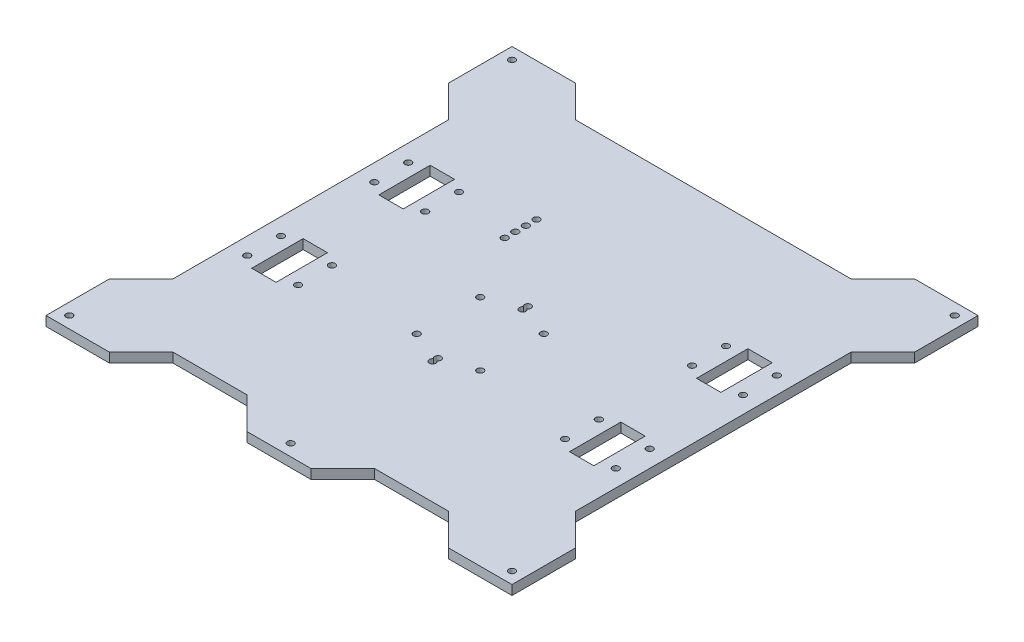
SolidWorks part; units mm, degrees
ref_plane "Front Plane" through (0, 0, 0) normal (0, 0, 1) x (1, 0, 0)
ref_plane "Top Plane" through (0, 0, 0) normal (0, 1, 0) x (1, 0, 0)
ref_plane "Right Plane" through (0, 0, 0) normal (1, 0, 0) x (0, 0, -1)
sketch "Sketch1" plane through (0, 0, 0) normal (0, 1, 0) x (1, 0, 0)
  line L1 (-110, 110) -> (110, 110)
  line L2 (-110, 110) -> (-110, -110)
  line L3 (-110, -110) -> (110, -110)
  line L4 (110, 110) -> (110, -110)
  line L5 (-110, 110) -> (110, -110) construction
  line L6 (-110, -110) -> (110, 110) construction
  point P0 (0, 0)
  dimension "D1" = 220
  dimension "D2" = 220
extrude "Square" add sketch "Sketch1" along normal blind 4.5
sketch "Sketch2" plane through (0, 4.5, 0) normal (0, 1, 0) x (1, 0, 0)
  line L0 (0, 110) -> (0, -110) construction
  line L1 (110, 110) -> (-110, 110) construction
  line L2 (-110, -110) -> (110, -110) construction
  line L3 (-110, 0) -> (110, 0) construction
  line L4 (-110, 110) -> (-110, -110) construction
  line L5 (110, -110) -> (110, 110) construction
  line L6 (75, 110) -> (75, -110) construction
  line L7 (75, 30) -> (0, 30) construction
  line L8 (75, -30) -> (0, -30) construction
  circle A0 centre (87, 38) radius 1.55
  circle A1 centre (87, 22) radius 1.55
  circle A2 centre (63, 22) radius 1.55
  circle A3 centre (63, 38) radius 1.55
  circle A4 centre (-63, 38) radius 1.55
  circle A5 centre (-63, 22) radius 1.55
  circle A6 centre (-87, 22) radius 1.55
  circle A7 centre (-87, 38) radius 1.55
  circle A8 centre (-87, 22) radius 1.55
  circle A9 centre (-87, 38) radius 1.55
  circle A10 centre (-63, 38) radius 1.55
  circle A11 centre (-63, 22) radius 1.55
  circle A12 centre (63, 22) radius 1.55
  circle A13 centre (63, 38) radius 1.55
  circle A14 centre (87, 38) radius 1.55
  circle A15 centre (87, 22) radius 1.55
  circle A16 centre (87, -22) radius 1.55
  circle A17 centre (87, -38) radius 1.55
  circle A18 centre (63, -38) radius 1.55
  circle A19 centre (63, -22) radius 1.55
  circle A20 centre (-63, -22) radius 1.55
  circle A21 centre (-63, -38) radius 1.55
  circle A22 centre (-87, -38) radius 1.55
  circle A23 centre (-87, -22) radius 1.55
  circle A24 centre (-87, -38) radius 1.55
  circle A25 centre (-87, -22) radius 1.55
  circle A26 centre (-63, -22) radius 1.55
  circle A27 centre (-63, -38) radius 1.55
  circle A28 centre (63, -38) radius 1.55
  circle A29 centre (63, -22) radius 1.55
  circle A30 centre (87, -22) radius 1.55
  circle A31 centre (87, -38) radius 1.55
  dimension "D6" = 3.1
  dimension "D7" = 3.1
  dimension "D1" = 75
  dimension "D2" = 30
  dimension "D3" = 16
  dimension "D5" = 12
extrude "LM8UU-Holders" cut sketch "Sketch2" against normal through all contours A7 | A6 | A5 | A4 | A20 | A21 | A22 | A23 | A19 | A18 | A17 | A16 | A1 | A0 | A3 | A2 region at (87, 4.5, -38) region at (87, 4.5, -22) region at (63, 4.5, -22) region at (63, 4.5, -38) region at (-63, 4.5, -38) region at (-63, 4.5, -22) region at (-87, 4.5, -22) region at (-87, 4.5, -38) region at (87, 4.5, 22) region at (87, 4.5, 38) region at (63, 4.5, 38) region at (63, 4.5, 22) region at (-63, 4.5, 22) region at (-63, 4.5, 38) region at (-87, 4.5, 38) region at (-87, 4.5, 22)
sketch "Sketch3" plane through (0, 4.5, 0) normal (0, 1, 0) x (1, 0, 0)
  line L0 (0, -110) -> (0, 110) construction
  line L1 (-110, -110) -> (110, -110) construction
  line L2 (110, 110) -> (-110, 110) construction
  line L3 (110, -15) -> (-110, -15) construction
  line L6 (15, -30) -> (-15, -30) construction
  line L7 (15, 0) -> (-15, 0) construction
  line L8 (110, -110) -> (110, 110) construction
  line L9 (-110, 110) -> (-110, -110) construction
  line L10 (110, 0) -> (-110, 0) construction
  circle A0 centre (-15, -30) radius 1.55
  circle A1 centre (15, -30) radius 1.55
  circle A2 centre (15, 0) radius 1.55
  circle A3 centre (-15, 0) radius 1.55
  point P16 (0, -30)
  dimension "D1" = 3.1
  dimension "D2" = 15
  dimension "D3" = 15
  dimension "D5" = 15
extrude "DefaultBelt" cut sketch "Sketch3" against normal through all
sketch "Sketch4" plane through (0, 4.5, 0) normal (0, 1, 0) x (1, 0, 0)
  line L0 (0, 110) -> (0, -110) construction
  line L1 (110, 110) -> (-110, 110) construction
  line L2 (-110, -110) -> (110, -110) construction
  line L3 (-15, -1.55) -> (-15, -28.45) construction
  line L4 (15, -28.45) -> (15, -1.55) construction
  line L5 (15, -15) -> (-15, -15) construction
  arc A0 (-0.9165, 6.25) -> (0.9165, 6.25) centre (0, 5) ccw
  arc A1 (0.9165, 6.25) -> (-0.9165, 6.25) centre (0, 7.5) ccw
  arc A2 (0.9165, -36.25) -> (-0.9165, -36.25) centre (0, -37.5) cw
  arc A3 (-0.9165, -36.25) -> (0.9165, -36.25) centre (0, -35) cw
  circle A4 centre (-15, 0) radius 1.55 construction
  circle A5 centre (-15, -30) radius 1.55 construction
  circle A6 centre (15, -30) radius 1.55 construction
  circle A7 centre (15, 0) radius 1.55 construction
  dimension "D1" = 3.1
  dimension "D2" = 3.1
  dimension "D3" = 20
  dimension "D4" = 22.5
extrude "BeltOptions" cut sketch "Sketch4" against normal through all
sketch "Sketch5" plane through (0, 4.5, 0) normal (0, 1, 0) x (1, 0, 0)
  line L0 (-110, 0) -> (110, 0) construction
  line L1 (-110, 110) -> (-110, -110) construction
  line L2 (110, -110) -> (110, 110) construction
  line L3 (0, 110) -> (0, -110) construction
  line L4 (110, 110) -> (-110, 110) construction
  line L5 (-110, 110) -> (-110, 80)
  line L6 (-110, 80) -> (-95, 65)
  line L7 (-95, 65) -> (-95, -65)
  line L8 (0, 0) -> (-110, 110) construction
  line L9 (-65, 95) -> (65, 95)
  line L10 (-80, 110) -> (-65, 95)
  line L11 (-110, 110) -> (-80, 110)
  line L12 (-95, 65) -> (-95, -65)
  line L13 (0, 0) -> (110, 110) construction
  line L14 (95, 65) -> (95, -65)
  line L15 (110, 110) -> (80, 110)
  line L16 (80, 110) -> (65, 95)
  line L17 (95, 65) -> (95, -65)
  line L18 (110, 80) -> (95, 65)
  line L19 (110, 110) -> (110, 80)
  line L20 (0, 0) -> (110, -110) construction
  line L21 (0, 0) -> (-110, -110) construction
  line L22 (110, -110) -> (110, -80)
  line L23 (110, -80) -> (95, -65)
  line L24 (80, -110) -> (65, -95)
  line L25 (110, -110) -> (80, -110)
  line L26 (-110, -110) -> (-80, -110)
  line L27 (-80, -110) -> (-65, -95)
  line L28 (-65, -95) -> (65, -95)
  line L29 (-110, -80) -> (-95, -65)
  line L30 (-110, -110) -> (-110, -80)
  point P24 (0, 95)
  point P32 (95, 0)
  point P35 (-95, 0)
  point P36 (0, -95)
  circle M16 centre (15, -30) radius 1.55
  circle M18 centre (63, 38) radius 1.55
  circle M20 centre (87, 22) radius 1.55
  circle M22 centre (87, -38) radius 1.55
  circle M23 centre (63, -38) radius 1.55
  circle M24 centre (63, -22) radius 1.55
  circle M25 centre (-87, -22) radius 1.55
  circle M26 centre (-87, -38) radius 1.55
  circle M27 centre (-63, -38) radius 1.55
  circle M28 centre (-63, -22) radius 1.55
  circle M29 centre (-63, 38) radius 1.55
  circle M30 centre (-63, 22) radius 1.55
  circle M31 centre (-87, 22) radius 1.55
  circle M32 centre (-87, 38) radius 1.55
  line M33 (110, -110) -> (110, 110)
  line M34 (110, 110) -> (-110, 110)
  line M35 (-110, 110) -> (-110, -110)
  line M36 (-110, -110) -> (110, -110)
  dimension "D1" = 15
  dimension "D2" = 30
  dimension "D3" = 45
  dimension "D4" = 45
extrude "Shaping" cut sketch "Sketch5" against normal blind 10 flip side to cut contours L29 L27 L28 L24 L23 L14 L18 L16 L9 L10 L6 L7 M35 M36 M33 M34 M16 M18 M20 M22 M24 M26 M28 M30 M32 M31 M29 M27 M25 M23 region at (0.0423, 4.5, -0.013)
sketch "Sketch6" plane through (0, 4.5, 0) normal (0, 1, 0) x (1, 0, 0)
  line L0 (-110, 110) -> (110, -110) construction
  line L1 (-110, -110) -> (110, 110) construction
  line L2 (110, 80) -> (110, 110) construction
  line L3 (0, 95) -> (0, -95) construction
  line L4 (-65, 95) -> (65, 95) construction
  line L5 (-65, -95) -> (65, -95) construction
  line L6 (-95, 0) -> (95, 0) construction
  line L7 (-95, 65) -> (-95, -65) construction
  line L8 (95, 65) -> (95, -65) construction
  circle A0 centre (-104.5, 104.5) radius 1.55
  circle A1 centre (104.5, 104.5) radius 1.55
  circle A2 centre (104.5, -104.5) radius 1.55
  circle A3 centre (-104.5, -104.5) radius 1.55
  dimension "D2" = 3.1
  dimension "D1" = 45
  dimension "D3" = 104.5
extrude "Cut-Extrude5" cut sketch "Sketch6" against normal through all
sketch "Sketch7" plane through (0, 4.5, 0) normal (0, 1, 0) x (1, 0, 0)
  line L0 (-87, 38) -> (-63, 22) construction
  line L1 (-63, 22) -> (-87, 22) construction
  line L2 (-87, 22) -> (-63, 38) construction
  line L3 (-63, 38) -> (-87, 38) construction
  line L4 (-95, 0) -> (95, 0) construction
  line L5 (-80.75, 42.125) -> (-69.25, 42.125)
  line L6 (-80.75, 42.125) -> (-80.75, 17.875)
  line L7 (-80.75, 17.875) -> (-69.25, 17.875)
  line L8 (-69.25, 42.125) -> (-69.25, 17.875)
  line L9 (-80.75, 42.125) -> (-69.25, 17.875) construction
  line L10 (-80.75, 17.875) -> (-69.25, 42.125) construction
  line L11 (-95, 65) -> (-95, -65) construction
  line L12 (95, 65) -> (95, -65) construction
  line L13 (0, -95) -> (0, 95) construction
  line L14 (-65, -95) -> (65, -95) construction
  line L15 (-65, 95) -> (65, 95) construction
  line L16 (-80.75, -17.875) -> (-69.25, -42.125) construction
  line L17 (-80.75, -42.125) -> (-69.25, -17.875) construction
  line L18 (-63, -38) -> (-87, -38) construction
  line L19 (-87, -22) -> (-63, -38) construction
  line L20 (-63, -22) -> (-87, -22) construction
  line L21 (-87, -38) -> (-63, -22) construction
  line L22 (-69.25, -42.125) -> (-69.25, -17.875)
  line L23 (-80.75, -17.875) -> (-69.25, -17.875)
  line L24 (-80.75, -42.125) -> (-80.75, -17.875)
  line L25 (-80.75, -42.125) -> (-69.25, -42.125)
  line L26 (-80.75, 17.875) -> (-69.25, 42.125) construction
  line L27 (80.75, 17.875) -> (69.25, 42.125) construction
  line L28 (87, -38) -> (63, -22) construction
  line L29 (63, -22) -> (87, -22) construction
  line L30 (87, -22) -> (63, -38) construction
  line L31 (63, -38) -> (87, -38) construction
  line L32 (80.75, -42.125) -> (69.25, -17.875) construction
  line L33 (80.75, -17.875) -> (69.25, -42.125) construction
  line L34 (80.75, 17.875) -> (69.25, 42.125) construction
  line L35 (80.75, 42.125) -> (69.25, 17.875) construction
  line L36 (63, 38) -> (87, 38) construction
  line L37 (87, 22) -> (63, 38) construction
  line L38 (63, 22) -> (87, 22) construction
  line L39 (87, 38) -> (63, 22) construction
  line L40 (80.75, -42.125) -> (69.25, -42.125)
  line L41 (80.75, -42.125) -> (80.75, -17.875)
  line L42 (80.75, -17.875) -> (69.25, -17.875)
  line L43 (69.25, -42.125) -> (69.25, -17.875)
  line L44 (69.25, 42.125) -> (69.25, 17.875)
  line L45 (80.75, 17.875) -> (69.25, 17.875)
  line L46 (80.75, 42.125) -> (80.75, 17.875)
  line L47 (80.75, 42.125) -> (69.25, 42.125)
  point P4 (-75, 30)
  point P33 (-75, -30)
  point P50 (75, -30)
  point P51 (75, 30)
  dimension "D1" = 11.5
  dimension "D2" = 24.25
extrude "Cut-Extrude6" cut sketch "Sketch7" against normal through all
sketch "Sketch8" plane through (0, 4.5, 0) normal (0, 1, 0) x (1, 0, 0)
  line L3 (-65, 95) -> (65, 95) construction
  line L4 (-33.45, 45) -> (-33.45, 30) construction
  circle A0 centre (-33.45, 45) radius 1.55
  circle A1 centre (-33.45, 40) radius 1.55
  circle A2 centre (-33.45, 35) radius 1.55
  circle A3 centre (-33.45, 30) radius 1.55
  dimension "D1" = 3.1
  dimension "D2" = 50
extrude "EndstopTrigger" cut sketch "Sketch8" against normal through all
pattern_linear "LPattern1" [suppressed] count 2 spacing 30 of bodies 108
sketch "Sketch9" plane through (0, 4.5, 0) normal (0, 1, 0) x (1, 0, 0)
  line L0 (-80, -110) -> (80, -110) construction
  line L1 (0, -110) -> (0, -95) construction
  line L2 (-65, -95) -> (65, -95) construction
  line L3 (15, -110) -> (-15, -110)
  line L4 (-15, -110) -> (-30, -95)
  line L5 (-30, -95) -> (30, -95)
  line L6 (-80, -110) -> (-65, -95) construction
  line L8 (-110, -110) -> (-80, -110) construction
  line L9 (15, -110) -> (30, -95)
  line L10 (-104.5, -104.5) -> (104.5, -104.5) construction
  circle A0 centre (0, -104.5) radius 1.55
  point P14 (-95, -110)
  dimension "D2" = 15
  dimension "D3" = 3.1
  dimension "D1" = 90
extrude "Boss-Extrude1" add sketch "Sketch9" against normal through all
equation "\"X-ROD-SPACING\"=45"
equation "\"Y-ROD-SPACING\"=75"
equation "\"Z-ROD-SPACING\"=17.5"
equation "\"Y-BED-OFFSET\"=2"
equation "\"Y-BED-ROD-INSET\"=3.5"
equation "\"T-SLOT-NUT-FILLET-RADIUS\"=0.25"
equation "\"T-SLOT-SCREW-SHAFT-RADIUS\"=1.75"
equation "\"T-SLOT-SCREW-SHAFT-CUTOUT-LENGTH\"=10.5"
equation "\"T-SLOT-NUT-DEPTH\"=4.2"
equation "\"T-SLOT-NUT-WIDTH\"=3"
equation "\"T-SLOT-NUT-END-DISTANCE\"=8"
equation "\"ACRYLIC-THICKNESS\"=10"
equation "\"ACRYLIC-THICKNESS2\"=4.5"
equation "\"ACRYLIC-TAB-CUTOUT-SIZE\"=\"ACRYLIC-THICKNESS\"+\"ACRYLIC-TAB-TOLERANCE\"*2"
equation "\"ACRYLIC-TAB-WIDTH\"=\"ACRYLIC-THICKNESS\""
equation "\"ACRYLIC-M3-HOLE\"=3.1"
equation "\"SMOOTHROD-CAP-SCREW-DISTANCE\"=20"
equation "\"FRAME-WIDTH-INNER\"=370"
equation "\"NEMA17-HOLE-SPACING\"=31"
equation "\"NEMA17-CENTRAL-CUTOUT\"=22.5"
equation "\"Z-BRACKET-REACH\"=55"
equation "\"TOP-BRACKET-SPACING\"=40"
equation "\"SMOOTHROD-X-LENGTH\"=350"
equation "\"SMOOTHROD-Y-LENGTH\"=350"
equation "\"SMOOTHROD-Z-LENGTH\"=350"
equation "\"SMOOTHROD-TIGHTENING-HEADROOM\"=.25"
equation "\"LEADSCREW-Z-LENGTH\"=300"
equation "\"SCREW-LENGTH-FRAME\"=\"ACRYLIC-THICKNESS\" + 10"
equation "\"SCREW-HEAD-RADIUS\"=6"
equation "\"PRINTED-X-SMOOTHROD-DIAMETER\"=8.2"
equation "\"PRINTED-X-SMOOTHROD-CUTOUT\"=10"
equation "\"PRINTED-X-BASE-HEIGHT\"=10"
equation "\"PRINTED-LM8UU-CUTOUT-SIZE\"=15.25"
equation "\"PRINTED-LM8UU-CUTOUT-LENGTH\"=24.5"
equation "\"PRINTED-X-IDLER-HEIGHT\"=16"
equation "\"PSU-MOUNTING-WIDTH\"=95"
equation "\"PSU-MOUNTING-HEIGHT\"=177"
equation "\"Y-BELT-TO-ROD-DISTANCE\"=20"
equation "\"D6@Sketch2\"=\"ACRYLIC-M3-HOLE\""
equation "\"D7@Sketch2\"=\"ACRYLIC-M3-HOLE\""
equation "\"D1@Sketch2\"=\"Y-ROD-SPACING\""
equation "\"D1@Sketch3\"=\"ACRYLIC-M3-HOLE\""
equation "\"D2@Sketch6\"=\"ACRYLIC-M3-HOLE\""
equation "\"Y-BED-SCREW-SPACING\"=209"
equation "\"Y-BED-SCREW-CUTOUT-SLOT-HEIGHT\"=2"
equation "\"ACRYLIC-TAB-TOLERANCE\"=.1"
equation "\"Z-ROD-INSET\"=16"
equation "\"SCREW-LENGTH-MOTOR\"=\"ACRYLIC-THICKNESS\" + 5"
equation "\"SCREW-LENGTH-EXTRUDER\"=28"
equation "\"PRINTED-M3-HOLE\"=3.5"
equation "\"SPOOL-HOLDER-ROD-SPACING\"=150"
equation "\"ACRYLIC-X-CARRIAGE-WIDTH\"=55"
equation "\"ACRYLIC-X-CARRIAGE-HEIGHT\"=75"
equation "\"ACRYLIC-X-CARRIAGE-LM8UU-CUTOUT-WIDTH\"=24.25"
equation "\"ACRYLIC-X-CARRIAGE-LM8UU-CUTOUT-HEIGHT\"=11.5"
equation "\"ACRYLIC-X-CARRIAGE-SCREW-SPACING-X\"=15"
equation "\"ACRYLIC-X-CARRIAGE-SCREW-SPACING-Y\"=33"
equation "\"ACRYLIC-X-CARRIAGE-CENTER-TAB-SPACING\"=14"
equation "\"ACRYLIC-X-CARRIAGE-EXTRUDER-OFFSET\"=26"
equation "\"ACRYLIC-X-CARRIAGE-EXTRUDER-ANGLE\"=90"
equation "\"ACRYLIC-X-CARRIAGE-EXTRUDER-SHELF-DEPTH\"=\"ACRYLIC-X-CARRIAGE-EXTRUDER-OFFSET\" + 28"
equation "\"ACRYLIC-X-CARRIAGE-EXTRUDER-BRACE-SPACING\"=23"
equation "\"ACRYLIC-X-CARRIAGE-EXTRUDER-BRACE-TAB-OFFSET\"=20"
equation "\"ACRYLIC-X-CARRIAGE-EXTRUDER-BRACE-HEIGHT\"=35"
equation "\"ACRYLIC-X-CARRIAGE-EXTRUDER-BRACE-SCREW-SPACING\"=22"
equation "\"ACRYLIC-X-CARRIAGE-DUAL-WIDTH-MULTIPLIER\"=1.65"
equation "\"ACRYLIC-X-CARRIAGE-DUAL-HOTEND-SPACING\"=42"
equation "\"ACRYLIC-X-CARRIAGE-DUAL-WIDTH\"=103"
equation "\"ACRYLIC-X-CARRIAGE-DUAL-HOTEND-SEPARATION\"=35"
equation "\"ACRYLIC-X-CARRIAGE-DUAL-MOUNT-PLATE-DEPTH\"=76"
equation "\"ACRYLIC-X-CARRIAGE-DUAL-MOUNT-BRACE-WIDTH\"=45"
equation "\"ACRYLIC-X-CARRIAGE-DUAL-MOUNT-SCREW-WIDTH\"=40"
equation "\"BLOWER-FAN-WIDTH\"=15"
equation "\"D1@Sketch7\"=\"ACRYLIC-X-CARRIAGE-LM8UU-CUTOUT-HEIGHT\""
equation "\"D2@Sketch7\"=\"ACRYLIC-X-CARRIAGE-LM8UU-CUTOUT-WIDTH\""
equation "\"D1@Sketch8\"=\"ACRYLIC-M3-HOLE\""
equation "\"D2@Sketch4\"=\"ACRYLIC-M3-HOLE\""
equation "\"D1@Sketch4\"=\"ACRYLIC-M3-HOLE\""
equation "\"D3@Sketch4\"=20"
equation "\"D3@Sketch9\"=\"ACRYLIC-M3-HOLE\""
